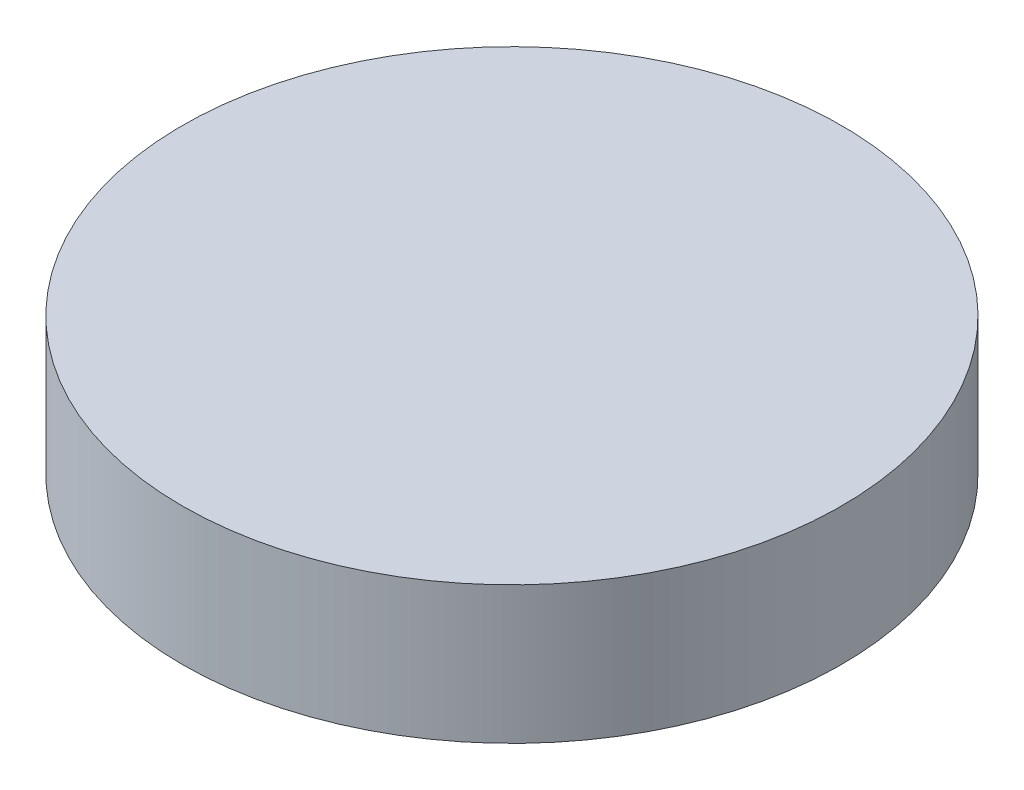
SolidWorks part; units mm, degrees
ref_plane "Front Plane" through (0, 0, 0) normal (0, 0, 1) x (1, 0, 0)
ref_plane "Top Plane" through (0, 0, 0) normal (0, 1, 0) x (1, 0, 0)
ref_plane "Right Plane" through (0, 0, 0) normal (1, 0, 0) x (0, 0, -1)
sketch "Sketch1" plane through (0, 0, 0) normal (0, 1, 0) x (1, 0, 0)
  circle A0 centre (0, 0) radius 24
extrude "Boss-Extrude1" add sketch "Sketch1" along normal blind 10
